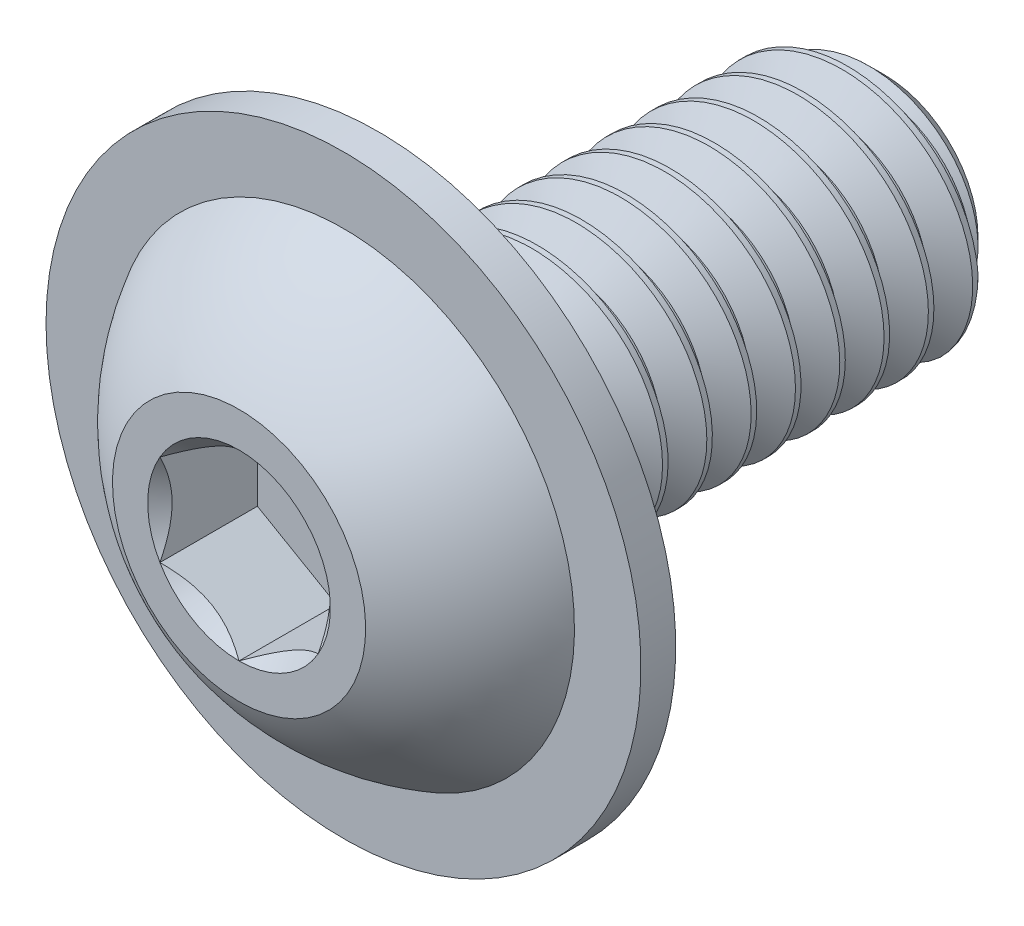
SolidWorks part; units mm, degrees
ref_plane "Front" through (0, 0, 0) normal (0, 0, 1) x (1, 0, 0)
ref_plane "Top" through (0, 0, 0) normal (0, 1, 0) x (1, 0, 0)
ref_plane "Right" through (0, 0, 0) normal (1, 0, 0) x (0, 0, -1)
sketch "Sketch1" plane through (0, 0, 0) normal (1, 0, 0) x (0, 0, -1)
  line L2 (2.2, 2) -> (10.2, 2)
  line L3 (10.2, 2) -> (10.2, 0)
  line L4 (10.2, 0) -> (2.2, 0)
  line L6 (1.65, 3.65) -> (2.2, 3.65) construction
  line L7 (10.2, 2) -> (10.2, -2) construction
  line L8 (0, 0) -> (2.2, 0) construction
  line L9 (2.2, 3.65) -> (2.2, -3.65) construction
  line L11 (2.2, 2) -> (2.2, 0)
  line L13 (0, 1.25) -> (0, -1.25) construction
  line L14 (0, 1.25) -> (0, 2) construction
  line L15 (1.65, 3.65) -> (1.65, 4.7) construction
  line L16 (1.65, 4.7) -> (2.2, 4.7) construction
  line L17 (2.2, 4.7) -> (2.2, 3.65) construction
  line L18 (2.2, 4.7) -> (2.2, -4.7) construction
  arc A3 (0, 2) -> (1.65, 3.65) centre (3.65, 0) cw construction
  dimension "D1" = 0.55
  dimension "Head Ht" = 2.2
  dimension "Head Dia" = 7.3
  dimension "Dia" = 4
  dimension "Lg" = 8
  dimension "Hex" = 2.5
  dimension "Flange Dia" = 9.4
revolve "Revolve1" add sketch "Sketch1" angle 360 about L4
sketch "Sketch3" plane through (0, 0, -10.2) normal (0, 0, -1) x (-1, 0, 0)
  circle A0 centre (0, 0) radius 2
curve "Helix/Spiral1" pitch 0.7 height 8.7 radius 2 centre (0, 0, -10.2) axis (0, 0, 1) start towards (0, 1, 0)
sketch "Sketch2" plane through (0, 0, 0) normal (1, 0, 0) x (0, 0, -1)
  line L0 (10.2, 2) -> (10.8125, 2)
  line L1 (10.8125, 2) -> (10.55, 1.5453)
  line L2 (10.55, 1.5453) -> (10.4625, 1.5453)
  line L3 (10.4625, 1.5453) -> (10.2, 2)
  line L4 (10.3313, 1.7727) -> (10.6813, 1.7727) construction
  dimension "D1" = 60
  dimension "D2" = 0.0875
  dimension "D3" = 0.35
chamfer "Chamfer1" distance 0.525 angle 45 1 edges at (0, 2, -10.2)
sweep "Cut-Sweep1" cut profiles "Sketch2" path "Helix/Spiral1"
sketch "Sketch7" plane through (0, 0, 0) normal (1, 0, 0) x (0, 0, -1)
  line L6 (1.65, 3.65) -> (2.2, 3.65) construction
  line L8 (0, 0) -> (2.2, 0) construction
  line L11 (2.2, 3.65) -> (2.2, -3.65) construction
  line L12 (1.65, 3.65) -> (2.2, 3.65)
  line L13 (0, 0) -> (2.2, 0)
  line L14 (0, 1.25) -> (0, -1.25) construction
  line L15 (2.2, 3.65) -> (2.2, 0)
  line L16 (0, 2) -> (0, 0)
  arc A2 (1.65, 3.65) -> (0, 2) centre (3.65, 0) ccw construction
  arc A3 (1.65, 3.65) -> (0, 2) centre (3.65, 0) ccw
revolve "Revolve2" add sketch "Sketch7" angle 360 about L13
sketch "Sketch11" plane through (0, 0, -2.2) normal (0, 0, -1) x (-1, 0, 0)
  circle A0 centre (0, 0) radius 4.7
extrude "Boss-Extrude3" add sketch "Sketch11" against normal up to vertex (0.55 mm away) up to point (0, 3.65, -1.65)
sketch "Sketch5" plane through (0, 0, 0) normal (0, 0, 1) x (1, 0, 0)
  line L1 (1.25, -0.7217) -> (1.25, 0.7217)
  line L2 (1.25, 0.7217) -> (0, 1.4434)
  line L3 (0, 1.4434) -> (-1.25, 0.7217)
  line L4 (-1.25, 0.7217) -> (-1.25, -0.7217)
  line L5 (-1.25, -0.7217) -> (0, -1.4434)
  line L6 (0, -1.4434) -> (1.25, -0.7217)
  circle A0 centre (0, 0) radius 1.25 construction
extrude "Cut-Extrude2" cut sketch "Sketch5" against normal blind 1.54
sketch "Sketch6" plane through (0, 0, 0) normal (0, 0, 1) x (1, 0, 0)
  circle A0 centre (0, 0) radius 1.4434
extrude "Cut-Extrude3" cut sketch "Sketch6" against normal blind 1.54 draft 45
sketch "Sketch9" [suppressed] plane through (0, 0, -5.0546) normal (0, 0, 1) x (1, 0, 0)
  circle A2 centre (0, 0) radius 4.7625
extrude "Boss-Extrude2" [suppressed] add sketch "Sketch9" against normal offset from surface (6.35 mm away) 31.75 up to face at (0, 1.475, -10.2)
sketch "Sketch10" plane through (0, 0, 0) normal (1, 0, 0) x (0, 0, -1)
  line L0 (10.2, 2) -> (10.2, -2) construction
  point P0 (9.15, -2)
  dimension "D1" = 1.05
equation "\"D3@Helix/Spiral1\" = \"Lg@Sketch1\" + \"D4@Helix/Spiral1\""
equation "\"D2@Sketch2\" = \"D4@Helix/Spiral1\" * .125"
equation "\"D3@Sketch2\" = \"D4@Helix/Spiral1\" * .5"
equation "\"D1@Chamfer1\" = \"D4@Helix/Spiral1\" * .75"
equation "\"D1@Cut-Extrude2\" = \"Head Ht@Sketch1\" * .7"
equation "\"D1@Sketch1\" = \"Head Ht@Sketch1\" * .25"
equation "\"D1@Sketch10\" = \"D4@Helix/Spiral1\" * 1.5"
equation "\"D1@Cut-Extrude3\" = \"D1@Cut-Extrude2\""
